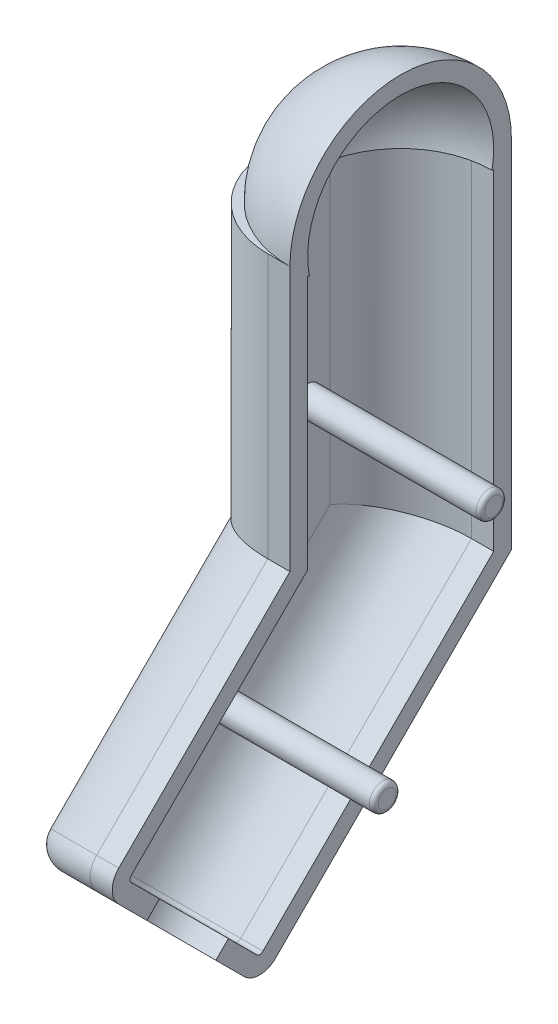
SolidWorks part; units mm, degrees
ref_plane "Front Plane" through (0, 0, 0) normal (0, 0, 1) x (1, 0, 0)
ref_plane "Top Plane" through (0, 0, 0) normal (0, 1, 0) x (1, 0, 0)
ref_plane "Right Plane" through (0, 0, 0) normal (1, 0, 0) x (0, 0, -1)
sketch "Sketch1" plane through (0, 0, 0) normal (1, 0, 0) x (0, 0, -1)
  line L0 (-12.5, 0) -> (12.5, 0)
  line L1 (-33.5876, -50.9099) -> (-15.9099, -68.5876)
  line L2 (-12.5, 0) -> (-12.5, -29.8223)
  line L3 (-12.5, -29.8223) -> (-33.5876, -50.9099)
  line L4 (12.5, 0) -> (12.5, -40.1777)
  line L5 (12.5, -40.1777) -> (-15.9099, -68.5876)
extrude "Boss-Extrude1" add sketch "Sketch1" along normal mid plane 25
sketch "Sketch2" plane through (0, 0, 0) normal (0, 0, 1) x (1, 0, 0)
  line L0 (0, 0) -> (0, 12.5)
  line L1 (0, 0) -> (-12.5, 0)
  arc A0 (0, 12.5) -> (-12.5, 0) centre (0, 0) ccw
revolve "Revolve1" add sketch "Sketch2" angle 360 about L0
fillet "Fillet1" radius 10 8 edges at (-12.5, -54.3826, 1.705) (-12.5, -20.0888, -12.5) (12.5, -54.3826, 1.705) (12.5, -20.0888, -12.5) (-12.5, -40.3661, 23.0438) (12.5, -40.3661, 23.0438) (12.5, -14.9112, 12.5) (-12.5, -14.9112, 12.5)
fillet "Fillet2" radius 2.5 8 edges at (-9.5711, -52.981, 31.5165) (-12.5, -59.7487, 24.7487) (-9.5711, -66.5165, 17.981) (0, -68.5876, 15.9099) (9.5711, -66.5165, 17.981) (12.5, -59.7487, 24.7487) (9.5711, -52.981, 31.5165) (0, -50.9099, 33.5876)
sketch "Sketch4" plane through (0, 0, 0) normal (0, 0, 1) x (1, 0, 0)
  line L0 (0, 17.0315) -> (0, -73.6851)
  line L4 (0, -73.6851) -> (31.3678, -73.6851)
  line L5 (31.3678, -73.6851) -> (31.3678, 17.0315)
  line L6 (31.3678, 17.0315) -> (0, 17.0315)
extrude "Cut-Extrude2" cut sketch "Sketch4" against normal mid plane 68.5
shell "Shell2" thickness 2 removed face at (0, -36.7115, 12.024)
sketch "Sketch6" plane through (-10.5, 0, 0) normal (-1, 0, 0) x (0, 0, 1)
  circle A0 centre (0, -24.45) radius 1.5
  circle A1 centre (12.0208, -47.0208) radius 1.5
extrude "Boss-Extrude3" add sketch "Sketch6" against normal blind 21
fillet "Fillet4" radius 0.5 2 edges at (10.5, -47.0208, 13.5208) (10.5, -24.45, 1.5)
sketch "Sketch7" plane through (0, -42.2487, 42.2487) normal (0, -0.7071, 0.7071) x (1, 0, 0)
  line L0 (0, -34.7487) -> (0, -14.7487) construction
  circle A0 centre (0, -24.7487) radius 5.5
extrude "Cut-Extrude3" cut sketch "Sketch7" against normal blind 5
